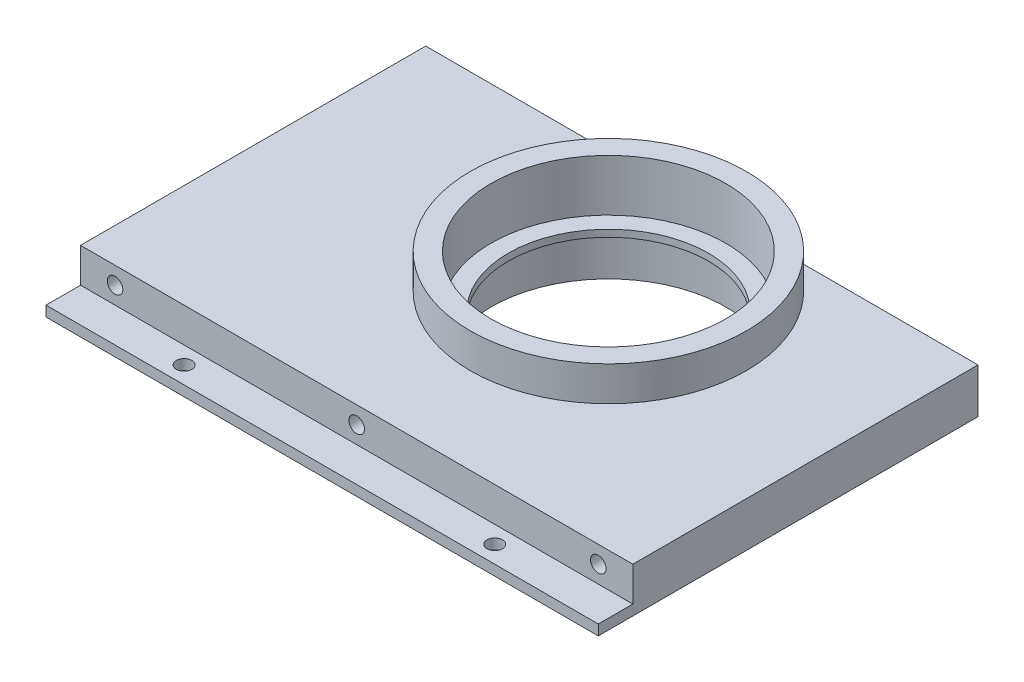
SolidWorks part; units mm, degrees
ref_plane "Front Plane" through (0, 0, 0) normal (0, 0, 1) x (1, 0, 0)
ref_plane "Top Plane" through (0, 0, 0) normal (0, 1, 0) x (1, 0, 0)
ref_plane "Right Plane" through (0, 0, 0) normal (1, 0, 0) x (0, 0, -1)
sketch "Sketch1" plane through (0, 0, 0) normal (0, 1, 0) x (1, 0, 0)
  line L0 (0, 0) -> (0, -65) construction
  line L1 (-27.081, 35) -> (-19.3649, 35)
  line L4 (0, -65) -> (72.08, -65)
  line L8 (0, -65) -> (-77.921, -65)
  line L12 (-77.921, 35) -> (-27.081, 35)
  line L14 (72.08, 35) -> (72.08, -65)
  line L15 (37.081, 35) -> (72.08, 35)
  line L16 (37.081, 35) -> (19.3649, 35)
  line L18 (-77.921, 35) -> (-87.921, 35)
  line L20 (-77.921, -65) -> (-87.921, -65)
  line L21 (-87.921, 35) -> (-87.921, -65)
  circle A0 centre (0, 0) radius 22.5 construction
  circle A1 centre (0, 0) radius 29
  circle A2 centre (0, 0) radius 34
  circle A3 centre (0, 0) radius 40
  point P14 (0, -40)
  point P16 (-77.921, -45)
  dimension "D1" = 45
  dimension "D2" = 58
  dimension "D3" = 68
  dimension "D5" = 58.5561
  dimension "D6" = 72.08
  dimension "D7" = 10
  dimension "D8" = 77.921
  dimension "D9" = 25
  dimension "D11" = 34.999
  dimension "D4" = 6
extrude "Boss-Extrude1" add sketch "Sketch1" along normal blind 15 contours A3 A2 region at (0, 0, -38.8686)
extrude "Boss-Extrude2" add sketch "Sketch1<3>" against normal blind 16 contours A3 A2 region at (0, 0, -38.8686)
sketch "Sketch1<3>" plane through (0, 0, 0) normal (0, 1, 0) x (1, 0, 0) same geometry as "Sketch1"
extrude "Boss-Extrude3" add sketch "Sketch1<4>" against normal blind 2 contours A2 A1 region at (-33.0383, 0, 0)
sketch "Sketch1<4>" plane through (0, 0, 0) normal (0, 1, 0) x (1, 0, 0) same geometry as "Sketch1"
extrude "Boss-Extrude4" add sketch "Sketch1<5>" along normal blind 5 and the other way blind 5 contours A3 L12 L8 L4 region at (-23.223, 0, -33.1132)
sketch "Sketch1<5>" plane through (0, 0, 0) normal (0, 1, 0) x (1, 0, 0) same geometry as "Sketch1"
sketch "Sketch2" plane through (0, 0, 65) normal (0, 0, 1) x (1, 0, 0)
  line L0 (-87.921, 0) -> (72.08, 0) construction
  line L2 (-7.9205, -5) -> (-7.9205, 5) construction
  line L3 (72.08, -5) -> (-87.921, -5) construction
  line L4 (72.08, 5) -> (-87.921, 5) construction
  line L6 (72.08, -5) -> (72.08, 5) construction
  line L7 (-87.921, -5) -> (-87.921, 5) construction
  circle A1 centre (-77.921, 0) radius 2.25
  circle A3 centre (-7.9205, 0) radius 2.25
  circle A4 centre (62.08, 0) radius 2.25
  point P2 (-87.921, 0)
  point P13 (-77.921, 0)
  dimension "D1" = 10
extrude "Cut-Extrude1" cut sketch "Sketch2" against normal blind 10
sketch "Sketch3" plane through (0, 5, 0) normal (0, 1, 0) x (1, 0, 0)
  line L0 (19.3649, 35) -> (62.079, 35)
  line L3 (-77.921, -75) -> (62.079, -75)
  line L6 (-77.921, -75) -> (-87.921, -75)
  line L8 (-19.3649, 35) -> (-87.921, 35)
  line L9 (-87.921, -75) -> (-87.921, 35)
  line L10 (62.079, -75) -> (72.08, -75)
  line L12 (62.079, 35) -> (72.08, 35)
  line L13 (72.08, -75) -> (72.08, 35)
  arc A0 (-19.3649, 35) -> (19.3649, 35) centre (0, 0) ccw
  point P14 (0, 0)
  point P16 (-77.921, 35)
  point P17 (-19.8554, 35)
  dimension "D2" = 80
  dimension "D1" = 110
  dimension "D3" = 160.001
extrude "Boss-Extrude5" add sketch "Sketch3" against normal blind 3 from surface starting at face at (-5.2803, -5, 10.8333)
sketch "Sketch4" plane through (0, -5, 0) normal (0, 1, 0) x (-1, 0, 0)
  line L0 (87.921, 70) -> (-72.08, 70) construction
  line L3 (7.9205, 75) -> (7.9205, 65) construction
  line L4 (-72.08, 75) -> (87.921, 75) construction
  line L5 (87.921, 65) -> (-72.08, 65) construction
  line L6 (87.921, 65) -> (87.921, 75) construction
  line L7 (-72.08, 75) -> (-72.08, 65) construction
  circle A2 centre (52.921, 70) radius 2.25
  circle A3 centre (-37.08, 70) radius 2.25
  point P2 (87.921, 70)
  point P4 (-72.08, 70)
  point P6 (7.9205, 70)
  point P7 (77.081, 90)
  point P8 (52.921, 70)
  dimension "D1" = 35
extrude "Cut-Extrude3" cut sketch "Sketch4" against normal blind 3
